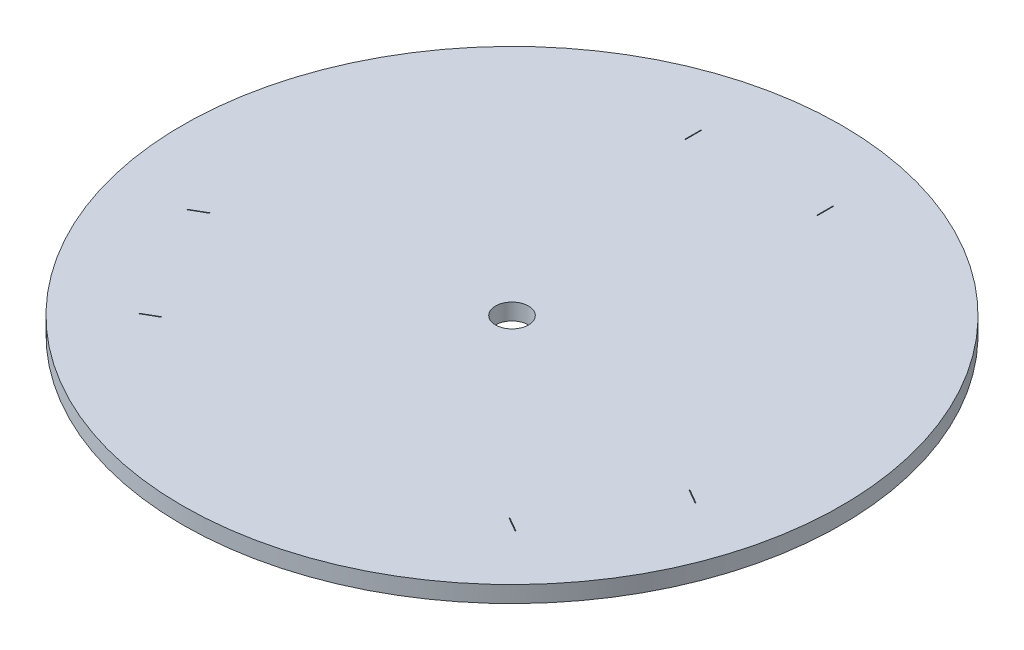
SolidWorks part; units mm, degrees
ref_plane "Front Plane" through (0, 0, 0) normal (0, 0, 1) x (1, 0, 0)
ref_plane "Top Plane" through (0, 0, 0) normal (0, 1, 0) x (1, 0, 0)
ref_plane "Right Plane" through (0, 0, 0) normal (1, 0, 0) x (0, 0, -1)
sketch "Sketch2" plane through (0, 0, 0) normal (0, 1, 0) x (1, 0, 0)
  circle A0 centre (0, 0) radius 100
  dimension "D1" = 200
extrude "Boss-Extrude1" add sketch "Sketch2" along normal blind 5
sketch "Sketch3" plane through (0, 5, 0) normal (0, 1, 0) x (1, 0, 0)
  line L0 (0, 0) -> (0, 100) construction
  line L1 (-20, 75) -> (20, 75) construction
  line L2 (72.8368, -18.8429) -> (77.167, -21.3429)
  line L3 (-20.1, 72.5) -> (-19.9, 72.5)
  line L4 (-20.1, 72.5) -> (-20.1, 77.5)
  line L5 (-20.1, 77.5) -> (-19.9, 77.5)
  line L6 (-19.9, 72.5) -> (-19.9, 77.5)
  line L7 (-20.1, 72.5) -> (-19.9, 77.5) construction
  line L8 (-20.1, 77.5) -> (-19.9, 72.5) construction
  line L9 (19.9, 72.5) -> (20.1, 72.5)
  line L10 (19.9, 72.5) -> (19.9, 77.5)
  line L11 (19.9, 77.5) -> (20.1, 77.5)
  line L12 (20.1, 72.5) -> (20.1, 77.5)
  line L13 (19.9, 72.5) -> (20.1, 77.5) construction
  line L14 (19.9, 77.5) -> (20.1, 72.5) construction
  line L15 (72.8368, -18.8429) -> (72.7368, -19.0161)
  line L16 (72.7368, -19.0161) -> (77.067, -21.5161)
  line L17 (77.167, -21.3429) -> (77.067, -21.5161)
  line L18 (52.8368, -53.4839) -> (57.167, -55.9839)
  line L19 (52.8368, -53.4839) -> (52.7368, -53.6571)
  line L20 (52.7368, -53.6571) -> (57.067, -56.1571)
  line L21 (57.167, -55.9839) -> (57.067, -56.1571)
  line L22 (-52.7368, -53.6571) -> (-57.067, -56.1571)
  line L23 (-52.7368, -53.6571) -> (-52.8368, -53.4839)
  line L24 (-52.8368, -53.4839) -> (-57.167, -55.9839)
  line L25 (-57.067, -56.1571) -> (-57.167, -55.9839)
  line L26 (-72.7368, -19.0161) -> (-77.067, -21.5161)
  line L27 (-72.7368, -19.0161) -> (-72.8368, -18.8429)
  line L28 (-72.8368, -18.8429) -> (-77.167, -21.3429)
  line L29 (-77.067, -21.5161) -> (-77.167, -21.3429)
  line L30 (0, 0) -> (-86.6025, -50) construction
  line L31 (-74.9019, -20.2661) -> (-55.0019, -54.7339) construction
  line L32 (0, 0) -> (86.6025, -50) construction
  line L33 (74.9019, -20.2661) -> (55.0019, -54.7339) construction
  circle A0 centre (0, 0) radius 100 construction
  point P8 (0, 75)
  point P36 (0, 0)
  dimension "D1" = 40
  dimension "D2" = 5
  dimension "D3" = 0.2
  dimension "D4" = 75
  dimension "D6" = 120
  dimension "D7" = 120
  dimension "D5" = 3
extrude "Cut-Extrude1" cut sketch "Sketch3" against normal through all
sketch "Sketch4" plane through (0, 0, 0) normal (0, 0, 1) x (1, 0, 0)
  line L0 (-100, 0) -> (0, 0)
  line L1 (0, 0) -> (0, -31.5299)
  line L2 (0, -31.5299) -> (26.4846, -31.5299) construction
  line L3 (-100, 0) -> (-128.8281, 20.1856) construction
  arc A0 (0, -31.5299) -> (-100, 0) centre (0, 142.8148) cw
  dimension "D1" = 35
revolve "Revolve1" [suppressed] add sketch "Sketch4" angle 360 about L1
sketch "Sketch8" plane through (0, 0, 0) normal (0, -1, 0) x (-1, 0, 0)
  point P0 (0, 0)
hole_wizard "Ø10.0mm Dowel Hole1" positions "Sketch8" profile "Sketch7" hole size "Ø10.0" standard "ANSI Metric" end condition through all
sketch "Sketch7" plane through (0, 0, 0) normal (1, 0, 0) x (0, 0, -1)
  line L0 (0, 0) -> (0, 5)
  line L1 (0, 5) -> (5, 5)
  line L2 (5, 5) -> (5, 0.025)
  line L3 (5, 0.025) -> (5.025, 0)
  line L5 (5.025, 0) -> (0, 0)
  line L6 (-5, 0.025) -> (-5.025, 0) construction
  line L11 (0, -6.35) -> (0, 107.95) construction
  dimension "Thru Hole Dia." = 10
  dimension "Thru Hole Depth" = 5
  dimension "Near C'Sink Dia." = 10.05
  dimension "Near C'Sink Angle" = 90
equation "\"Leg_Spacing\"=40"
equation "\"D1@Sketch3\"=\"Leg_Spacing\""
equation "\"Leaf_Spring_Slot_Width\"=5"
equation "\"D2@Sketch3\"=\"Leaf_Spring_Slot_Width\""
equation "\"Leaf_Spring_Thickness\"=0.2"
equation "\"D3@Sketch3\"=\"Leaf_Spring_Thickness\""
equation "\"Inner_Radius\"=75"
equation "\"D4@Sketch3\"=\"Inner_Radius\""
equation "\"Camera\"=120"
